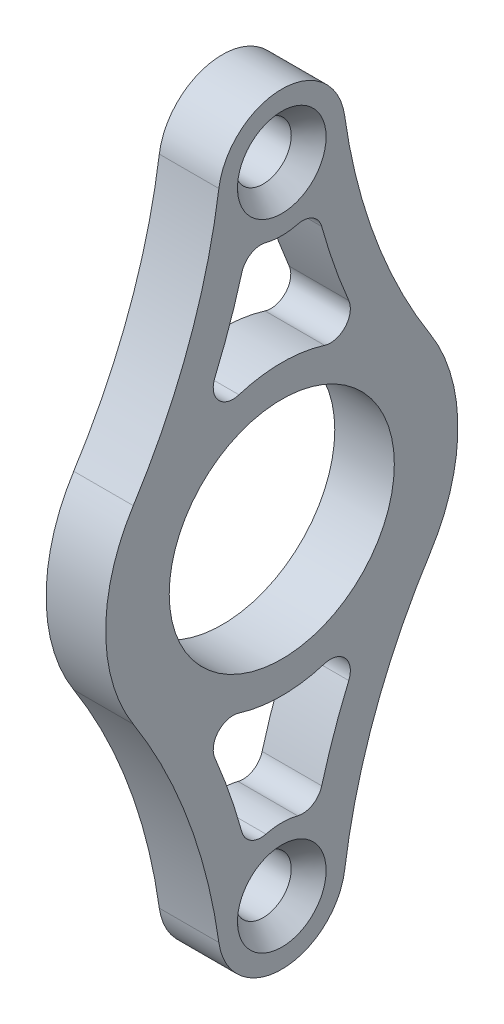
SolidWorks part; units mm, degrees
material "6061-T6 (SS)"
ref_plane "Front Plane" through (0, 0, 0) normal (0, 0, 1) x (1, 0, 0)
ref_plane "Top Plane" through (0, 0, 0) normal (0, 1, 0) x (1, 0, 0)
ref_plane "Right Plane" through (0, 0, 0) normal (1, 0, 0) x (0, 0, -1)
ref_plane "Plane1" through (54.442, 0, 0) normal (-1, 0, 0) x (0, 0, 1)
sketch "Sketch1" plane through (54.442, 0, 0) normal (-1, 0, 0) x (0, 0, 1)
  line L0 (-51.1134, 32.5835) -> (-5.0306, 26.107) construction
  line L1 (-23.0873, 0) -> (0, 0) construction
  line L2 (0, 0) -> (0, 25.4) construction
  circle A0 centre (0, -25.4) radius 2.2479 construction
  circle A1 centre (0, 25.4) radius 2.2479 construction
  circle A2 centre (0, -25.4) radius 2.2479
  circle A3 centre (0, 25.4) radius 2.2479
  circle A4 centre (0, 0) radius 9
  circle A5 centre (0, 0) radius 6 construction
  arc A6 (-11.8728, 7.5686) -> (-11.8728, -7.5686) centre (0, 0) ccw
  arc A7 (5.0306, 26.107) -> (-5.0306, 26.107) centre (0, 25.4) ccw
  arc A8 (-5.0306, -26.107) -> (5.0306, -26.107) centre (0, -25.4) ccw
  arc A9 (-5.0306, 26.107) -> (-11.8728, 7.5686) centre (-51.1134, 32.5835) cw
  arc A10 (5.0306, 26.107) -> (11.8728, 7.5686) centre (51.1134, 32.5835) ccw
  arc A11 (5.0306, -26.107) -> (11.8728, -7.5686) centre (51.1134, -32.5835) cw
  arc A12 (-5.0306, -26.107) -> (-11.8728, -7.5686) centre (-51.1134, -32.5835) ccw
  arc A13 (11.8728, -7.5686) -> (11.8728, 7.5686) centre (0, 0) ccw
  dimension "D1" = 18
  dimension "D2" = 12
  dimension "D4" = 10.16
  dimension "D3" = 5.08
  dimension "D5" = 8
extrude "Boss-Extrude1" add sketch "Sketch1" along normal blind 4.7625
sketch "Sketch2" plane through (49.6795, 0, 0) normal (-1, 0, 0) x (0, 0, 1)
  arc A0 (-9.1955, 5.8619) -> (-1.8865, 25.6651) centre (-51.1134, 32.5835) ccw
  arc A1 (1.8865, 25.6651) -> (-1.8865, 25.6651) centre (0, 25.4) ccw
  arc A2 (1.8865, 25.6651) -> (9.1955, 5.8619) centre (51.1134, 32.5835) ccw
  arc A3 (9.1955, -5.8619) -> (9.1955, 5.8619) centre (0, 0) ccw
  arc A4 (9.1955, -5.8619) -> (1.8865, -25.6651) centre (51.1134, -32.5835) ccw
  arc A5 (-1.8865, -25.6651) -> (1.8865, -25.6651) centre (0, -25.4) ccw
  arc A6 (-1.8865, -25.6651) -> (-9.1955, -5.8619) centre (-51.1134, -32.5835) ccw
  arc A7 (-9.1955, 5.8619) -> (-9.1955, -5.8619) centre (0, 0) ccw
  arc A8 (-11.8728, 7.5686) -> (-5.0306, 26.107) centre (-51.1134, 32.5835) ccw
  arc A9 (-11.8728, 7.5686) -> (-11.8728, -7.5686) centre (0, 0) ccw
  arc A10 (-5.0306, -26.107) -> (-11.8728, -7.5686) centre (-51.1134, -32.5835) ccw
  arc A11 (-5.0306, -26.107) -> (5.0306, -26.107) centre (0, -25.4) ccw
  arc A12 (11.8728, -7.5686) -> (5.0306, -26.107) centre (51.1134, -32.5835) ccw
  arc A13 (11.8728, -7.5686) -> (11.8728, 7.5686) centre (0, 0) ccw
  arc A14 (5.0306, 26.107) -> (11.8728, 7.5686) centre (51.1134, 32.5835) ccw
  arc A15 (5.0306, 26.107) -> (-5.0306, 26.107) centre (0, 25.4) ccw
  arc A16 (-11.8728, 7.5686) -> (-5.0306, 26.107) centre (-51.1134, 32.5835) ccw construction
  arc A17 (-11.8728, 7.5686) -> (-11.8728, -7.5686) centre (0, 0) ccw construction
  arc A18 (-5.0306, -26.107) -> (-11.8728, -7.5686) centre (-51.1134, -32.5835) ccw construction
  arc A19 (-5.0306, -26.107) -> (5.0306, -26.107) centre (0, -25.4) ccw construction
  arc A20 (11.8728, -7.5686) -> (5.0306, -26.107) centre (51.1134, -32.5835) ccw construction
  arc A21 (11.8728, -7.5686) -> (11.8728, 7.5686) centre (0, 0) ccw construction
  arc A22 (5.0306, 26.107) -> (11.8728, 7.5686) centre (51.1134, 32.5835) ccw construction
  arc A23 (5.0306, 26.107) -> (-5.0306, 26.107) centre (0, 25.4) ccw construction
  circle A24 centre (0, 0) radius 11.54
  circle A25 centre (0, 25.4) radius 5.08
  circle A26 centre (0, -25.4) radius 5.08
  circle A27 centre (0, 0) radius 9 construction
  dimension "D3" = 2.54
  dimension "D1" = 0
  dimension "D2" = 3.175
extrude "Cut-Extrude1" cut sketch "Sketch2" against normal through all contours A25 A0 A24 A2 | A26 A4 A24 A6 region at (49.6795, 15.0199, 0) region at (49.6795, -15.0199, 0)
fillet "Fillet1" radius 1.5875 8 edges at (52.0607, 8.8063, 7.4579) (52.0607, 8.8063, -7.4579) (52.0607, 21.1234, 2.7417) (52.0607, -8.8063, -7.4579) (52.0607, -8.8063, 7.4579) (52.0607, -21.1234, 2.7417) (52.0607, -21.1234, -2.7417) (52.0607, 21.1234, -2.7417)
sketch "Sketch5" plane through (54.442, 0, 0) normal (-1, 0, 0) x (0, 0, 1)
  point P0 (0, 25.4)
  point P3 (0, -25.4)
hole_wizard "CSK for #6 Flat Head Machine Screw1" positions "Sketch5" profile "Sketch4" countersink size "#6" standard "ANSI Inch"
sketch "Sketch4" plane through (54.442, 25.4, 0) normal (0, 1, 0) x (0, 0, -1)
  line L0 (0, 0) -> (0, 7.6434)
  line L1 (0, 7.6434) -> (2.1526, 6.35)
  line L2 (2.1526, 6.35) -> (2.1526, 1.5998)
  line L3 (2.1526, 1.5998) -> (3.5433, 0)
  line L5 (3.5433, 0) -> (0, 0)
  line L6 (-2.1526, 1.5998) -> (-3.5433, 0) construction
  line L10 (0, 7.6434) -> (-2.1526, 6.35) construction
  line L11 (0, -6.35) -> (0, 107.95) construction
  dimension "Hole Dia." = 4.3053
  dimension "Hole Depth" = 6.35
  dimension "Near C'Sink Dia." = 7.0866
  dimension "Near C'Sink Angle" = 82
  dimension "Drill Angle" = 118
equation "\"D1@Sketch1\"=18mm"
equation "\"D2@Sketch1\"=12mm"
